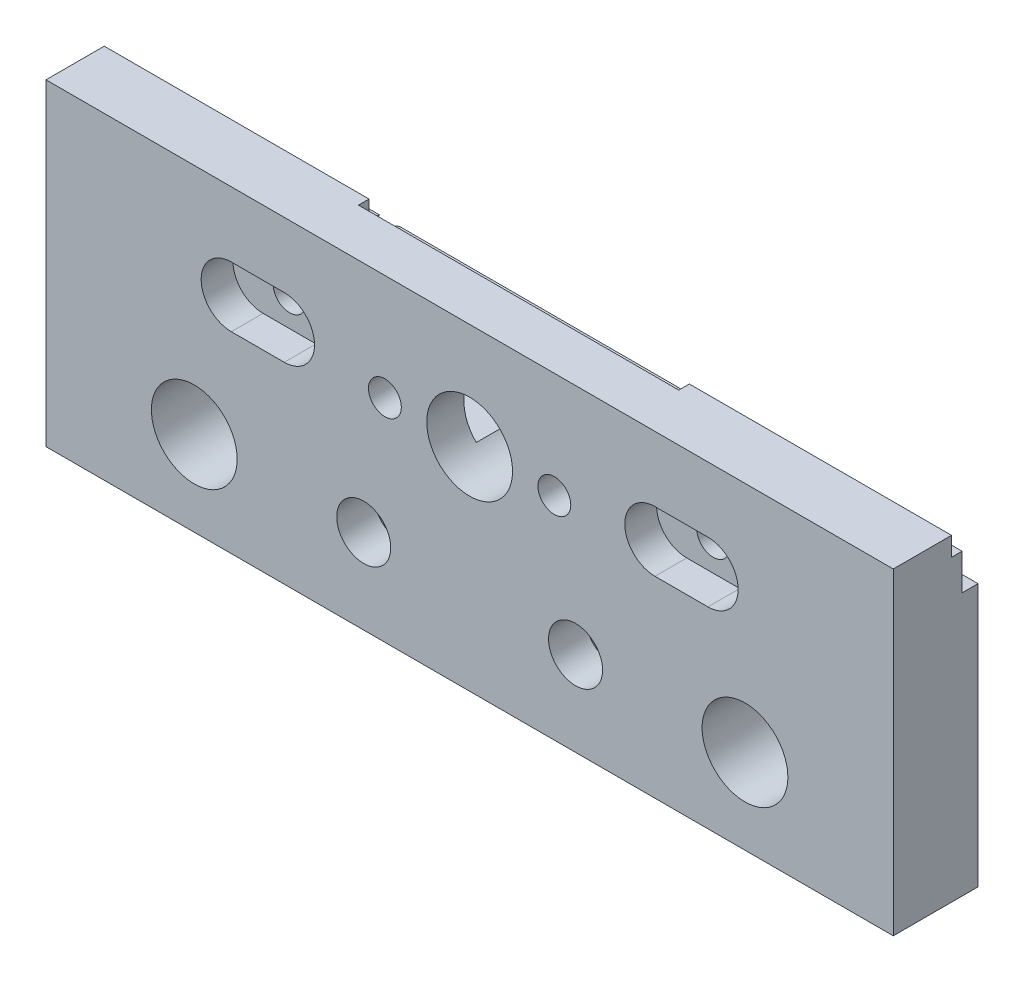
SolidWorks part; units mm, degrees
ref_plane "前视基准面" through (0, 0, 0) normal (0, 0, 1) x (1, 0, 0)
ref_plane "上视基准面" through (0, 0, 0) normal (0, 1, 0) x (1, 0, 0)
ref_plane "右视基准面" through (0, 0, 0) normal (1, 0, 0) x (0, 0, -1)
sketch "前视图草图" plane through (0, 0, 0) normal (0, 0, 1) x (1, 0, 0)
  line L0 (0, 0) -> (44.4821, 0) construction
  line L1 (0, 0) -> (0, 28.3185) construction
sketch "草图2" plane through (0, 0, 0) normal (0, 0, 1) x (1, 0, 0)
  line L0 (0, 0) -> (80, 0)
  line L1 (-200000, 0) -> (200044.4821, 0) construction
  line L2 (80, 0) -> (80, 30)
  line L3 (80, 30) -> (0, 30)
  line L4 (0, -200000) -> (0, 200028.3185) construction
  line L5 (0, 30) -> (0, 0)
  circle A0 centre (14, 8) radius 4.05
  circle A1 centre (40, 20) radius 4.05
  circle A2 centre (66, 8) radius 4.05
  dimension "D3" = 8
  dimension "D5" = 20
  dimension "D9" = 8.1
  dimension "D10" = 8.1
  dimension "D11" = 8.1
  dimension "D1" = 30
  dimension "D2" = 80
  dimension "D4" = 14
  dimension "D6" = 14
  dimension "D7" = 8
  dimension "D8" = 40
extrude "凸台-拉伸1" add sketch "草图2" along normal blind 8
sketch "草图3" plane through (0, 0, 8) normal (0, 0, 1) x (1, 0, 0)
  line L0 (16.088, 8) -> (31.4805, 8) construction
  line L1 (14, 8) -> (14, 16.8386) construction
  line L2 (66, 8) -> (66, 16.5917) construction
  line L4 (-200000, 0) -> (200044.4821, 0) construction
  circle A2 centre (30, 8) radius 2.55
  circle A3 centre (50, 8) radius 2.55
  dimension "D4" = 5.1
  dimension "D5" = 5.1
  dimension "D1" = 8
  dimension "D2" = 16
  dimension "D3" = 16
extrude "切除-拉伸1" cut sketch "草图3" against normal through all
sketch "草图4" plane through (80, 0, 0) normal (1, 0, 0) x (0, 0, -1)
  line L1 (0, -200000) -> (0, 200028.3185) construction
  line L2 (-1.5, 28.2) -> (-2.5, 28.2)
  line L3 (-2.5, 28.2) -> (-2.5, 30)
  line L4 (-8, 30) -> (0, 30) construction
  line L5 (-2.5, 30) -> (0, 30)
  line L6 (-1.5, 28.2) -> (-1.5, 24.8)
  line L7 (-1.5, 24.8) -> (0, 24.8)
  line L8 (0, 24.8) -> (0, 30)
  dimension "D1" = 3.4
  dimension "D2" = 2.5
  dimension "D3" = 1.5
  dimension "D4" = 1.8
extrude "切除-拉伸2" cut sketch "草图4" against normal through all
sketch "草图5" plane through (0, 0, 8) normal (0, 0, 1) x (1, 0, 0)
  line L0 (40, 20) -> (56.5376, 20) construction
  circle A0 centre (40, 20) radius 8 construction
  circle A1 centre (48, 20) radius 1.55
  circle A2 centre (32, 20) radius 1.55
  dimension "D1" = 3.1
  dimension "D2" = 3.1
  dimension "D3" = 16
extrude "切除-拉伸3" cut sketch "草图5" against normal through all
sketch "草图7" plane through (0, 0, 0) normal (0, 0, -1) x (-1, 0, 0)
  line L0 (-50, 10) -> (-50, -2.9965) construction
  line L1 (-30, 10) -> (-30, -2.3368) construction
  line L2 (200000, 0) -> (-200044.4821, 0) construction
  line L3 (-54.05, 10) -> (-54.05, 2.5)
  line L4 (-45.95, 10) -> (-45.95, 2.5)
  line L5 (-43.45, 0) -> (-56.55, 0)
  line L6 (-34.05, 10) -> (-34.05, 2.5)
  line L7 (-36.55, 0) -> (-23.45, 0)
  line L8 (-25.95, 2.5) -> (-25.95, 10)
  arc A0 (-45.95, 10) -> (-54.05, 10) centre (-50, 10) ccw
  arc A1 (-25.95, 10) -> (-34.05, 10) centre (-30, 10) ccw
  arc A2 (-56.55, 0) -> (-54.05, 2.5) centre (-56.55, 2.5) ccw
  arc A3 (-45.95, 2.5) -> (-43.45, 0) centre (-43.45, 2.5) ccw
  arc A4 (-36.55, 0) -> (-34.05, 2.5) centre (-36.55, 2.5) ccw
  arc A5 (-25.95, 2.5) -> (-23.45, 0) centre (-23.45, 2.5) ccw
  dimension "D1" = 8.1
  dimension "D4" = 8.1
  dimension "D5" = 2.5
  dimension "D6" = 2.5
  dimension "D7" = 2.5
  dimension "D8" = 2.5
  dimension "D2" = 10
  dimension "D3" = 10
extrude "切除-拉伸4" cut sketch "草图7" against normal blind 4.5
sketch "草图8" plane through (0, 0, 0) normal (0, 0, -1) x (-1, 0, 0)
  line L0 (-40, 20) -> (-57.3165, 20) construction
  line L1 (-40, 20) -> (-40, 35.6562) construction
  line L2 (-30, 22.85) -> (-50, 22.85)
  line L3 (-50, 17.15) -> (-30, 17.15)
  arc A0 (-30, 17.15) -> (-30, 22.85) centre (-30, 20) ccw
  arc A1 (-50, 22.85) -> (-50, 17.15) centre (-50, 20) ccw
  dimension "D1" = 5.7
  dimension "D2" = 10
  dimension "D3" = 10
extrude "切除-拉伸5" cut sketch "草图8" against normal blind 4.5
sketch "草图11" plane through (0, 0, 0) normal (0, 0, -1) x (-1, 0, 0)
  line L0 (-40, 20) -> (-58.6363, 20) construction
  line L1 (-80, 0) -> (-80, 24.8) construction
  line L2 (0, -200000) -> (0, 200028.3185) construction
  line L3 (-40, 20) -> (-40, 13.5744) construction
  line L4 (-28.772, 21) -> (-45.9396, 21) construction
  circle A0 centre (-60, 21) radius 1.55
  circle A1 centre (-20, 21) radius 1.55
  point P23 (-40, 20)
  dimension "D1" = 3.1
  dimension "D2" = 3.1
  dimension "D3" = 20
  dimension "D4" = 20
  dimension "D5" = 1
extrude "切除-拉伸7" cut sketch "草图11" against normal through all contours A0 | A1 region at (60, 21, 0) region at (20, 21, 0)
sketch "草图12" plane through (0, 0, 0) normal (0, 0, -1) x (-1, 0, 0)
  line L0 (-62.5, 18.15) -> (-57.5, 18.15)
  line L1 (-57.5, 23.85) -> (-62.5, 23.85)
  line L4 (-40, 20) -> (-42.9914, 20) construction
  line L5 (-39.1423, 21) -> (-43.2672, 21) construction
  line L6 (-60, 21) -> (-60, 25.2385) construction
  line L7 (-20, 21) -> (-20, 26.1603) construction
  line L8 (-40, 20) -> (-40, 24.3689) construction
  line L9 (-17.5, 23.85) -> (-22.5, 23.85)
  line L10 (-22.5, 18.15) -> (-17.5, 18.15)
  arc A0 (-62.5, 23.85) -> (-62.5, 18.15) centre (-62.5, 21) ccw
  arc A1 (-57.5, 18.15) -> (-57.5, 23.85) centre (-57.5, 21) ccw
  arc A4 (-17.5, 18.15) -> (-17.5, 23.85) centre (-17.5, 21) ccw
  arc A5 (-22.5, 23.85) -> (-22.5, 18.15) centre (-22.5, 21) ccw
  point P16 (-38, 21)
  point P28 (-40, 21)
  dimension "D2" = 1
  dimension "D3" = 5
  dimension "D4" = 2.5
  dimension "D1" = 2
extrude "切除-拉伸8" cut sketch "草图12" against normal blind 3
sketch "草图15" plane through (0, 0, 8) normal (0, 0, 1) x (1, 0, 0)
  line L2 (57.5, 18.15) -> (62.5, 18.15)
  line L3 (62.5, 23.85) -> (57.5, 23.85)
  line L4 (57.5, 18.15) -> (62.5, 18.15)
  line L5 (62.5, 23.85) -> (57.5, 23.85)
  line L6 (22.5, 23.85) -> (17.5, 23.85)
  line L7 (17.5, 18.15) -> (22.5, 18.15)
  line L8 (22.5, 23.85) -> (17.5, 23.85)
  line L9 (17.5, 18.15) -> (22.5, 18.15)
  arc A2 (62.5, 18.15) -> (62.5, 23.85) centre (62.5, 21) ccw
  arc A3 (57.5, 23.85) -> (57.5, 18.15) centre (57.5, 21) ccw
  arc A4 (62.5, 18.15) -> (62.5, 23.85) centre (62.5, 21) ccw
  arc A5 (57.5, 23.85) -> (57.5, 18.15) centre (57.5, 21) ccw
  arc A6 (17.5, 23.85) -> (17.5, 18.15) centre (17.5, 21) ccw
  arc A7 (22.5, 18.15) -> (22.5, 23.85) centre (22.5, 21) ccw
  arc A8 (17.5, 23.85) -> (17.5, 18.15) centre (17.5, 21) ccw
  arc A9 (22.5, 18.15) -> (22.5, 23.85) centre (22.5, 21) ccw
  dimension "D1" = 0
  dimension "D2" = 0
extrude "切除-拉伸9" cut sketch "草图15" against normal blind 3
sketch "草图19" plane through (0, 0, 2.5) normal (0, 0, -1) x (-1, 0, 0)
  line L0 (0, 30) -> (-80, 30) construction
  line L1 (-25, 30) -> (-55.2479, 30)
  line L2 (-25, 30) -> (-25, 28.3912)
  line L3 (-27.0396, 28.2) -> (-53.2083, 28.2)
  line L4 (-55.2479, 30) -> (-55.2479, 28.3912)
  line L5 (0, -200000) -> (0, 200028.3185) construction
  line L6 (0, 28.2) -> (-80, 28.2) construction
  line L7 (0, 28.2) -> (-80, 28.2) construction
  line L8 (-56.3335, 26.7) -> (-52.9089, 26.7) construction
  line L9 (-55.2479, 1028.5823) -> (-55.2479, 28.3912) construction
  line L10 (-25, 1028.5823) -> (-25, 28.3912) construction
  line L11 (-55.2479, 28.2) -> (-55.2479, -973.3) construction
  line L12 (-25, 28.2) -> (-25, -973.3) construction
  arc A10 (-55.6939, 27.7056) -> (-54.1796, 26.9619) centre (-55.2479, 26.7) ccw
  arc A11 (-26.0684, 26.9619) -> (-24.5541, 27.7056) centre (-25, 26.7) ccw
  arc A12 (-25, 28.3912) -> (-24.5541, 27.7056) centre (-24.25, 28.3912) ccw
  arc A13 (-26.0684, 26.9619) -> (-27.0396, 28.2) centre (-27.0396, 27.2) ccw
  arc A14 (-53.2083, 28.2) -> (-54.1796, 26.9619) centre (-53.2083, 27.2) ccw
  arc A15 (-55.6939, 27.7056) -> (-55.2479, 28.3912) centre (-55.9979, 28.3912) ccw
  dimension "D3" = 2.2
  dimension "D4" = 1.5
  dimension "D5" = 2
  dimension "D6" = 1.5
  dimension "D7" = 2
  dimension "D2" = 2.2
  dimension "D1" = 1.5
  dimension "D9" = 25
extrude "切除-拉伸11" cut sketch "草图19" against normal mid plane 2
